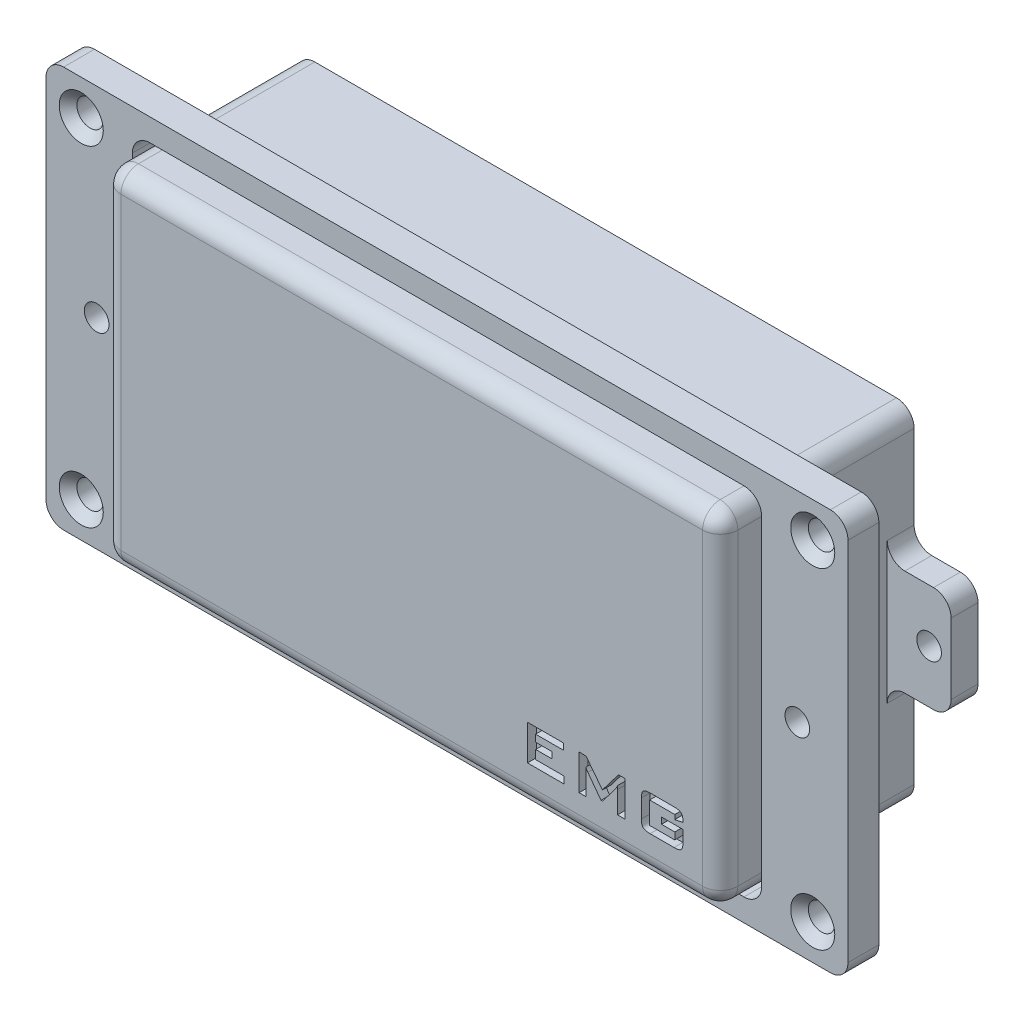
SolidWorks part; units mm, degrees
ref_plane "Спереди" through (0, 0, 0) normal (0, 0, 1) x (1, 0, 0)
ref_plane "Сверху" through (0, 0, 0) normal (0, 1, 0) x (1, 0, 0)
ref_plane "Справа" through (0, 0, 0) normal (1, 0, 0) x (0, 0, -1)
sketch "Эскиз1" plane through (0, 0, 0) normal (0, 0, 1) x (1, 0, 0)
  line L1 (-35, -19.5) -> (35, -19.5)
  line L2 (-35, -19.5) -> (-35, 19.5)
  line L3 (-35, 19.5) -> (35, 19.5)
  line L4 (35, -19.5) -> (35, 19.5)
  line L5 (-35, -19.5) -> (35, 19.5) construction
  line L6 (-35, 19.5) -> (35, -19.5) construction
  point P0 (0, 0)
  dimension "D1" = 70
  dimension "D2" = 39
extrude "Бобышка-Вытянуть1" add sketch "Эскиз1" against normal blind 22
sketch "Эскиз2" plane through (0, 0, -22) normal (0, 0, -1) x (-1, 0, 0)
  line L0 (0, 0) -> (0, 11.385)
  line L1 (42.25, -6) -> (-42.25, -6)
  line L2 (42.25, -6) -> (42.25, 6)
  line L3 (42.25, 6) -> (-42.25, 6)
  line L4 (-42.25, -6) -> (-42.25, 6)
  line L5 (42.25, -6) -> (-42.25, 6) construction
  line L6 (42.25, 6) -> (-42.25, -6) construction
  line L7 (42.25, 0) -> (39.75, 0)
  line L8 (-42.25, 0) -> (-39.75, 0)
  circle A0 centre (-39.75, 0) radius 1.4
  circle A1 centre (39.75, 0) radius 1.4
  point P0 (0, 0)
  line M1 (-35, 19.5) -> (-35, -19.5)
  line M3 (35, -19.5) -> (35, 19.5)
  dimension "D1" = 84.5
  dimension "D2" = 12
extrude "Бобышка-Вытянуть2" add sketch "Эскиз2" against normal blind 3.05 contours A1 L2 L3 L1 M3 | A0 L4 L1 L3 M1 region at (-38.625, -5.8598, -22) region at (38.625, -5.8598, -22)
sketch "Эскиз3" plane through (0, 0, 0) normal (0, 0, 1) x (1, 0, 0)
  line L0 (35, 0) -> (35.7, 0)
  line L1 (-45.5, 22.75) -> (45.5, 22.75)
  line L2 (-45.5, 22.75) -> (-45.5, -22.75)
  line L3 (-45.5, -22.75) -> (45.5, -22.75)
  line L4 (45.5, 22.75) -> (45.5, -22.75)
  line L5 (-45.5, 22.75) -> (45.5, -22.75) construction
  line L6 (-45.5, -22.75) -> (45.5, 22.75) construction
  line L7 (35, -19.5) -> (35, 19.5) construction
  line L8 (0, -19.5) -> (0, -20.2)
  line L9 (-35, -19.5) -> (35, -19.5) construction
  line L11 (-35.7, 20.2) -> (35.7, 20.2)
  line L12 (-35.7, 20.2) -> (-35.7, -20.2)
  line L13 (-35.7, -20.2) -> (35.7, -20.2)
  line L14 (35.7, 20.2) -> (35.7, -20.2)
  line L15 (-35.7, 20.2) -> (35.7, -20.2) construction
  line L16 (-35.7, -20.2) -> (35.7, 20.2) construction
  point P0 (0, 0)
  point P14 (0, 0)
  dimension "D1" = 45.5
  dimension "D2" = 91
extrude "Бобышка-Вытянуть3" add sketch "Эскиз3" against normal blind 7.5 separate body contours L4 L1 L2 L3 L11 L14 L13 L12 region at (0, 21.7326, 0)
sketch "Эскиз4" plane through (0, 0, 0) normal (0, 0, 1) x (1, 0, 0)
  line L1 (-45.5, 22.75) -> (45.5, 22.75)
  line L2 (-45.5, 22.75) -> (-45.5, -22.75)
  line L3 (-45.5, -22.75) -> (45.5, -22.75)
  line L4 (45.5, 22.75) -> (45.5, -22.75)
  line L5 (-45.5, 22.75) -> (45.5, -22.75) construction
  line L6 (-45.5, -22.75) -> (45.5, 22.75) construction
  line L7 (-35.7, 20.2) -> (35.7, 20.2)
  line L8 (-35.7, 20.2) -> (-35.7, -20.2)
  line L9 (-35.7, -20.2) -> (35.7, -20.2)
  line L10 (35.7, 20.2) -> (35.7, -20.2)
  line L11 (-35.7, 20.2) -> (35.7, -20.2) construction
  line L12 (-35.7, -20.2) -> (35.7, 20.2) construction
  point P0 (0, 0)
  point P7 (0, 0)
extrude "Вырез-Вытянуть1" cut sketch "Эскиз4" against normal blind 4
sketch "Эскиз5" plane through (0, 0, -22) normal (0, 0, -1) x (-1, 0, 0)
  circle A0 centre (-39.75, 0) radius 1.4
  circle A1 centre (39.75, 0) radius 1.4
extrude "Вырез-Вытянуть2" cut sketch "Эскиз5" against normal blind 64
sketch "Эскиз6" plane through (0, 0, -4) normal (0, 0, 1) x (1, 0, 0)
  line L0 (0, 0) -> (0, -5.9915)
  line L1 (-7.5078, 0) -> (7.439, 0)
  line L2 (45.5, -17.3557) -> (41.5, -17.3557)
  line L3 (45.5, -22.75) -> (45.5, 22.75) construction
  line L4 (41.5, -22.75) -> (41.5, -18.75)
  line L5 (-45.5, -22.75) -> (45.5, -22.75) construction
  circle A0 centre (41.5, -18.75) radius 1.5
  circle A1 centre (-41.5, -18.75) radius 1.5
  circle A2 centre (-41.5, 18.75) radius 1.5
  circle A3 centre (41.5, 18.75) radius 1.5
extrude "Вырез-Вытянуть3" cut sketch "Эскиз6" against normal blind 10 contours A3 | A0 | A1 | A2 region at (42.5307, -19.7807, -4) region at (-41.5, -18.75, -4) region at (-41.5, 18.75, -4) region at (41.5, 18.75, -4)
fillet "Скругление1" radius 2 8 edges at (-35, 19.5, -11) (35, 19.5, -11) (35, -19.5, -11) (-35, -19.5, -11) (0, 19.5, 0) (-35, 0, 0) (0, -19.5, 0) (35, 0, 0)
fillet "Скругление2" radius 2 4 edges at (45.5, 22.75, -5.75) (-45.5, 22.75, -5.75) (-45.5, -22.75, -5.75) (45.5, -22.75, -5.75)
fillet "Скругление3" radius 2 4 edges at (-35.7, 20.2, -5.75) (-35.7, -20.2, -5.75) (35.7, -20.2, -5.75) (35.7, 20.2, -5.75)
chamfer "Фаска1" distance 1 angle 45 4 edges at (-40, -18.75, -4) (-40, 18.75, -4) (43, 18.75, -4) (43, -18.75, -4)
sketch "Эскиз7" plane through (0, 0, 0) normal (0, 0, 1) x (1, 0, 0)
  text T0 "EMG" font "BankGothic Md BT" height 4
extrude "Вырез-Вытянуть4" cut sketch "Эскиз7" against normal blind 1
fillet "Скругление4" radius 2 8 edges at (-42.25, 6, -20.475) (-42.25, -6, -20.475) (42.25, -6, -20.475) (42.25, 6, -20.475)
sketch "Эскиз8" plane through (0, 0, -22) normal (0, 0, -1) x (-1, 0, 0)
  line L1 (-33, -17.5) -> (33, -17.5)
  line L2 (-33, -17.5) -> (-33, 17.5)
  line L3 (-33, 17.5) -> (33, 17.5)
  line L4 (33, -17.5) -> (33, 17.5)
  line L5 (-33, -17.5) -> (33, 17.5) construction
  line L6 (-33, 17.5) -> (33, -17.5) construction
  point P0 (0, 0)
extrude "Вырез-Вытянуть5" cut sketch "Эскиз8" against normal blind 1
sketch "Эскиз9" plane through (0, 0, -7.5) normal (0, 0, -1) x (-1, 0, 0)
  line L2 (35.1142, -19.6142) -> (-35.1142, -19.6142)
  line L4 (35.1142, -19.6142) -> (35.1142, 19.6142)
  line L5 (44, 21.25) -> (-44, 21.25)
  line L6 (44, 21.25) -> (44, -21.25)
  line L7 (44, -21.25) -> (-44, -21.25)
  line L8 (-44, 21.25) -> (-44, -21.25)
  line L9 (44, 21.25) -> (-44, -21.25) construction
  line L10 (44, -21.25) -> (-44, 21.25) construction
  line L11 (35.1142, 19.6142) -> (-35.1142, 19.6142)
  line L12 (-35.1142, -19.6142) -> (-35.1142, 19.6142)
  line L13 (35.1142, -19.6142) -> (-35.1142, 19.6142) construction
  line L14 (35.1142, 19.6142) -> (-35.1142, -19.6142) construction
  arc A0 (-33.7, 20.2) -> (-35.7, 18.2) centre (-33.7, 18.2) ccw construction
  point P0 (0, 0)
  point P8 (0, 0)
sketch "Эскиз10" plane through (0, 0, -4) normal (0, 0, 1) x (1, 0, 0)
extrude "Вырез-Вытянуть6" cut sketch "Эскиз9" against normal blind 1
sketch "Эскиз11" plane through (0, 0, -6.5) normal (0, 0, -1) x (-1, 0, 0)
  circle A0 centre (-41.5, 18.75) radius 2
  circle A1 centre (-41.5, -18.75) radius 2
  circle A2 centre (41.5, -18.75) radius 2
  circle A3 centre (41.5, 18.75) radius 2
  circle A4 centre (41.5, 18.75) radius 1.5
  circle A5 centre (41.5, -18.75) radius 1.5
  circle A6 centre (-41.5, -18.75) radius 1.5
  circle A7 centre (-41.5, 18.75) radius 1.5
extrude "Бобышка-Вытянуть4" add sketch "Эскиз11" along normal blind 1
